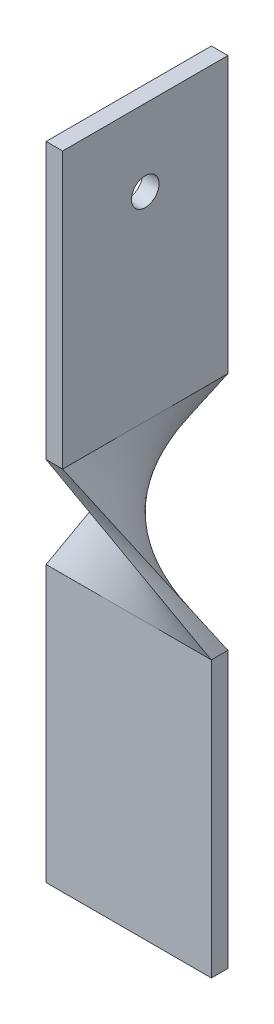
SolidWorks part; units mm, degrees
material "1060 Alloy"
ref_plane "Front Plane" through (0, 0, 0) normal (0, 0, 1) x (1, 0, 0)
ref_plane "Top Plane" through (0, 0, 0) normal (0, 1, 0) x (1, 0, 0)
ref_plane "Right Plane" through (0, 0, 0) normal (1, 0, 0) x (0, 0, -1)
sketch "Sketch1" plane through (0, 0, 0) normal (0, 1, 0) x (1, 0, 0)
  line L1 (0, 0) -> (30, 0)
  line L2 (0, 0) -> (0, 3)
  line L3 (0, 3) -> (30, 3)
  line L4 (30, 0) -> (30, 3)
  dimension "D1" = 30
  dimension "D2" = 3
extrude "Boss-Extrude1" add sketch "Sketch1" along normal blind 50
sketch "Sketch2" plane through (0, 50, 0) normal (0, 1, 0) x (1, 0, 0)
  line L0 (0, 3) -> (0, 0) construction
  line L1 (13.5, 16.5) -> (16.5, 16.5)
  line L2 (13.5, 16.5) -> (13.5, -13.5)
  line L3 (13.5, -13.5) -> (16.5, -13.5)
  line L4 (16.5, 16.5) -> (16.5, -13.5)
  line L6 (30, 3) -> (0, 3) construction
  point P6 (0, 1.5)
  point P7 (13.5, 1.5)
  point P10 (15, 3)
  point P11 (15, 16.5)
  dimension "D1" = 3
  dimension "D2" = 30
extrude "Boss-Extrude2" add sketch "Sketch2" along normal blind 50 from offset 30 separate body
loft "Loft1" add section face at (15, 50, -1.5) section face at (15, 80, -1.5) connector at (0, 50, -3) connector at (16.5, 80, -16.5)
sketch "Sketch3" plane through (13.5, 0, 0) normal (-1, 0, 0) x (0, 0, 1)
  line L0 (-16.5, 130) -> (13.5, 130) construction
  circle A0 centre (-1.5, 116.1121) radius 2.5
  point P2 (-1.7916, 110.8799)
  point P5 (-1.5, 130)
  point P6 (-1.5, 116.1121)
  dimension "D1" = 5
extrude "Cut-Extrude1" cut sketch "Sketch3" against normal blind 50
